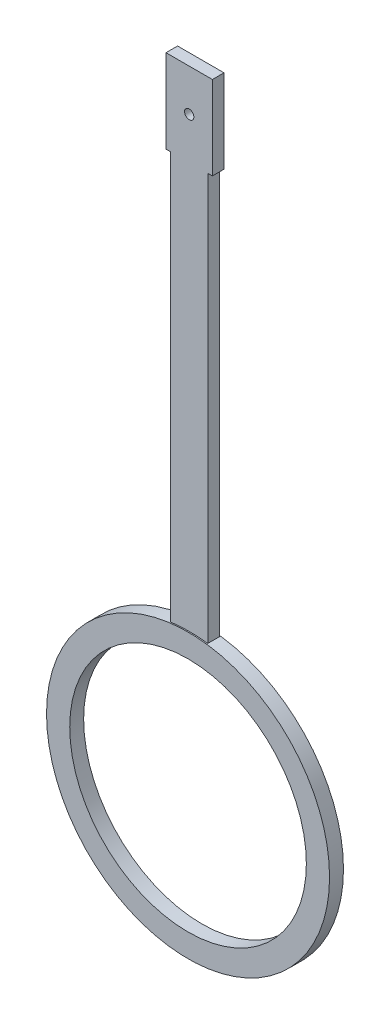
SolidWorks part; units mm, degrees
material "Gray Cast Iron"
ref_plane "Front Plane" through (0, 0, 0) normal (0, 0, 1) x (1, 0, 0)
ref_plane "Top Plane" through (0, 0, 0) normal (0, 1, 0) x (1, 0, 0)
ref_plane "Right Plane" through (0, 0, 0) normal (1, 0, 0) x (0, 0, -1)
sketch "Sketch1" plane through (0, 0, 0) normal (0, 0, 1) x (1, 0, 0)
  circle A0 centre (0, 0) radius 30.5
  dimension "D1" = 61
extrude "Boss-Extrude1" add sketch "Sketch1" along normal mid plane 3
sketch "Sketch2" plane through (0, 0, 0) normal (0, 0, 1) x (1, 0, 0)
  line L0 (-4, 25) -> (4, 25)
  line L1 (4, 25) -> (4, 118)
  line L2 (4, 118) -> (-4, 118)
  line L3 (-4, 118) -> (-4, 25)
extrude "Boss-Extrude2" add sketch "Sketch2" along normal mid plane 2.5
sketch "Sketch3" plane through (0, 0, 0) normal (0, 0, 1) x (1, 0, 0)
  line L0 (-5, 118) -> (5, 118)
  line L1 (5, 118) -> (5, 136)
  line L2 (5, 136) -> (-5, 136)
  line L3 (-5, 136) -> (-5, 118)
extrude "Boss-Extrude3" add sketch "Sketch3" along normal mid plane 2.5
sketch "Sketch4" plane through (0, 0, 0) normal (0, 0, 1) x (1, 0, 0)
  circle A0 centre (0, 0) radius 25.5
  dimension "D1" = 51
extrude "Cut-Extrude1" cut sketch "Sketch4" against normal mid plane 20
sketch "Sketch5" plane through (0, 0, 0) normal (0, 0, 1) x (1, 0, 0)
  circle A0 centre (0, 127) radius 1
  dimension "D1" = 2
extrude "Cut-Extrude2" cut sketch "Sketch5" against normal mid plane 20
